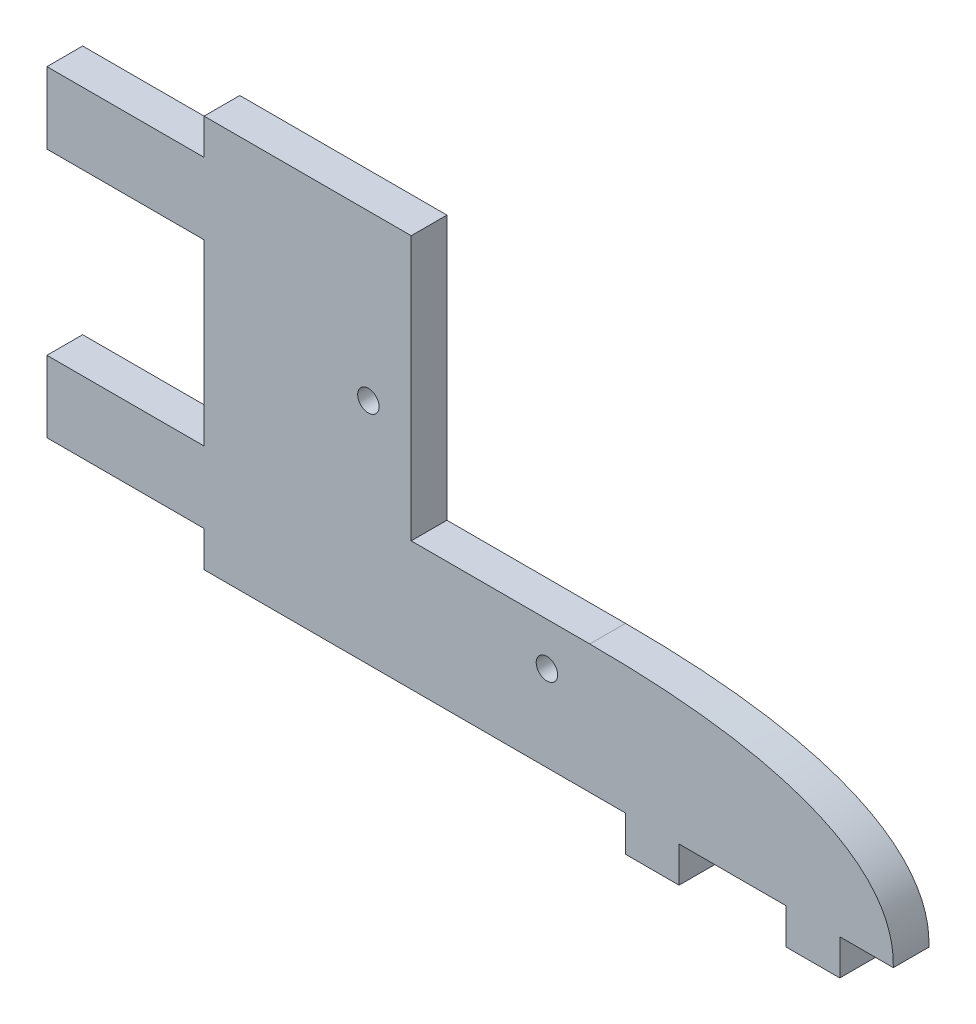
SolidWorks part; units mm, degrees
ref_plane "Plan de face" through (0, 0, 0) normal (0, 0, 1) x (1, 0, 0)
ref_plane "Plan de dessus" through (0, 0, 0) normal (0, 1, 0) x (1, 0, 0)
ref_plane "Plan de droite" through (0, 0, 0) normal (1, 0, 0) x (0, 0, -1)
sketch "Esquisse1" plane through (0, 0, 0) normal (0, 0, 1) x (1, 0, 0)
  line L1 (0, 0) -> (37, 0)
  line L2 (0, 0) -> (0, 55)
  line L3 (0, 55) -> (12, 55)
  line L4 (37, 0) -> (37, 18)
  line L6 (12, 55) -> (12, 18)
  line L7 (12, 18) -> (37, 18)
  circle A0 centre (6, 32) radius 1.5
  circle A1 centre (31, 12) radius 1.5
  dimension "D3" = 20
  dimension "D4" = 3
  dimension "D1" = 6
  dimension "D2" = 55
  dimension "D5" = 12
  dimension "D7" = 25
  dimension "D8" = 6
  dimension "D9" = 6
extrude "Boss.-Extru.1" add sketch "Esquisse1" along normal blind 5
sketch "Esquisse2" plane through (0, 0, 5) normal (0, 0, 1) x (1, 0, 0)
  line L0 (37, 18) -> (12, 18) construction
  line L1 (37, 0) -> (42, 0)
  line L2 (37, 0) -> (37, 18)
  line L3 (49.5, 0) -> (64.5, 0)
  line L4 (12, 55) -> (0, 55) construction
  line L5 (72, 0) -> (72, -5)
  line L6 (72, -5) -> (64.5, -5)
  line L7 (64.5, 0) -> (64.5, -5)
  line L8 (72, 0) -> (79.5, 0)
  line L9 (49.5, 0) -> (49.5, -5)
  line L10 (49.5, -5) -> (42, -5)
  line L11 (42, 0) -> (42, -5)
  line L12 (0, 0) -> (-17, 0)
  line L13 (0, 0) -> (0, 55)
  line L14 (0, 55) -> (-17, 55)
  line L15 (-17, 50) -> (-17, 55)
  line L16 (-17, 5) -> (-39, 5)
  line L17 (-17, 15) -> (-17, 40)
  line L19 (-17, 15) -> (-39, 15)
  line L20 (-17, 0) -> (-17, 5)
  line L21 (-39, 5) -> (-39, 15)
  line L22 (-17, 50) -> (-39, 50)
  line L24 (-17, 40) -> (-39, 40)
  line L25 (-39, 50) -> (-39, 40)
  spline S0 degree 3 poles (37, 18) (79.2395, 18) (79.5, 3.8743) (79.5, 0) knots 0 0 0 0 1 1 1 1
  dimension "D1" = 42.5
  dimension "D2" = 7.5
  dimension "D3" = 5
  dimension "D4" = 5
  dimension "D5" = 15
  dimension "D8" = 10
  dimension "D9" = 5
  dimension "D10" = 25
  dimension "D11" = 22
  dimension "D12" = 17
extrude "Boss.-Extru.2" add sketch "Esquisse2" against normal blind 5
